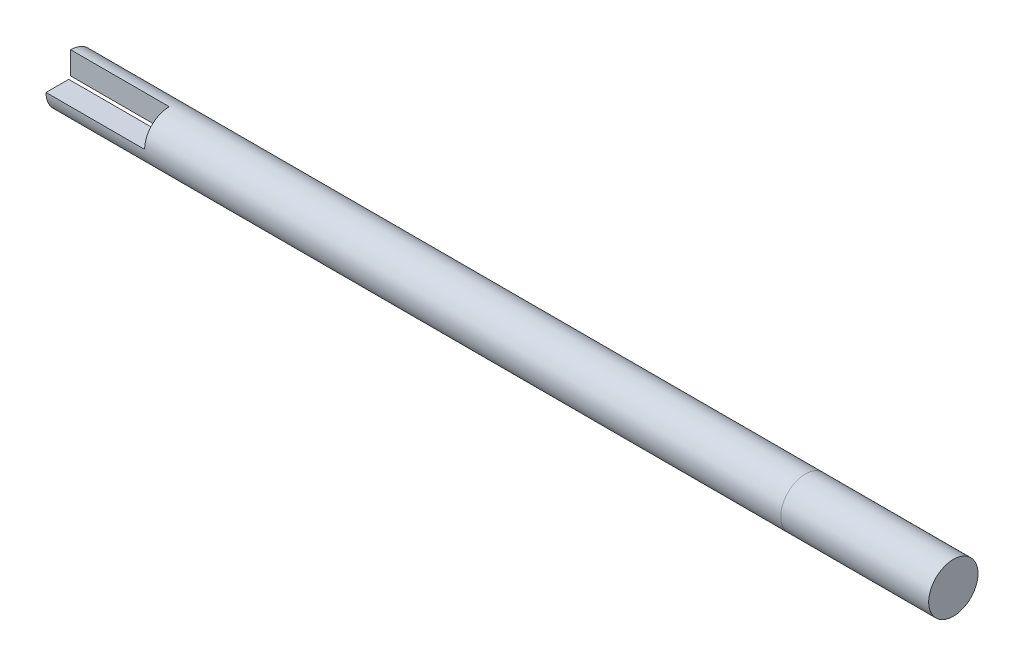
SolidWorks part; units mm, degrees
ref_plane "Front Plane" through (0, 0, 0) normal (0, 0, 1) x (1, 0, 0)
ref_plane "Top Plane" through (0, 0, 0) normal (0, 1, 0) x (1, 0, 0)
ref_plane "Right Plane" through (0, 0, 0) normal (1, 0, 0) x (0, 0, -1)
sketch "Sketch1" plane through (0, 0, 0) normal (0, 1, 0) x (1, 0, 0)
  line L0 (324.7028, 0) -> (339.7028, 0)
  line L1 (324.7028, 0) -> (250.2046, 0)
  line L2 (250.2046, -2.5) -> (250.2046, 2.5) construction
  dimension "D1" = 15
  dimension "D2" = 89.4983
sweep "Sweep1" add path "Sketch1" circular profile diameter 5 parameters "D3"=5
sketch "Sketch4" plane through (250.2046, 0, 0) normal (-1, 0, 0) x (0, 0, -1)
  line L0 (-2.5, 0) -> (-0.195, 0)
  line L1 (0, 2.5) -> (0, 0.195)
  line L2 (0.195, 0) -> (2.5, 0)
  line L3 (0, -0.195) -> (0, -2.5)
  arc A1 (-2.5, 0) -> (0, -2.5) centre (0, 0) ccw
  arc A2 (2.5, 0) -> (0, 2.5) centre (0, 0) ccw
  circle A5 centre (0, 0) radius 2.5 construction
  arc A6 (0, -0.195) -> (0.195, 0) centre (0, 0) ccw
  arc A7 (0, 0.195) -> (-0.195, 0) centre (0, 0) ccw
  point P5 (0.7914, 0.0977)
  point P9 (0.7914, 0.0977)
extrude "Cut-Extrude1" cut sketch "Sketch4" against normal blind 10
